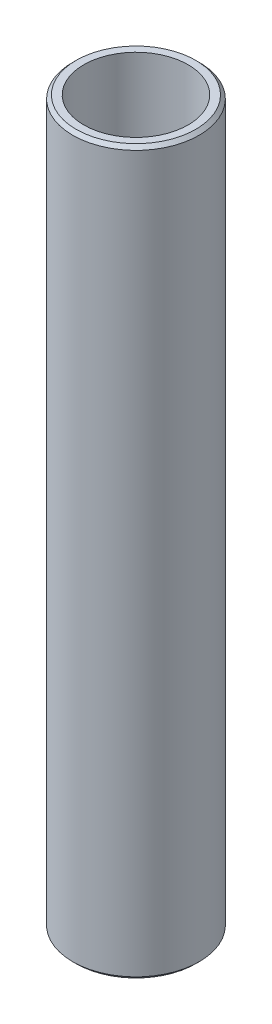
SolidWorks part; units mm, degrees
ref_plane "Front Plane" through (0, 0, 0) normal (0, 0, 1) x (1, 0, 0)
ref_plane "Top Plane" through (0, 0, 0) normal (0, 1, 0) x (1, 0, 0)
ref_plane "Right Plane" through (0, 0, 0) normal (1, 0, 0) x (0, 0, -1)
sketch "Sketch1" plane through (0, 0, 0) normal (0, 1, 0) x (1, 0, 0)
  circle A0 centre (0, 0) radius 52.5
  dimension "SHAFT_OD" = 105
extrude "Boss-Extrude1" add sketch "Sketch1" along normal blind 600
sketch "Sketch2" plane through (0, 0, 0) normal (0, 1, 0) x (1, 0, 0)
  circle A0 centre (0, 0) radius 43.3384
  dimension "BORE_D" = 86.6768
extrude "Cut-Extrude1" cut sketch "Sketch2" along normal through all
chamfer "Chamfer1" distance 2.8355 angle 45 2 edges at (0, 600, 52.5) (0, 0, 52.5)
